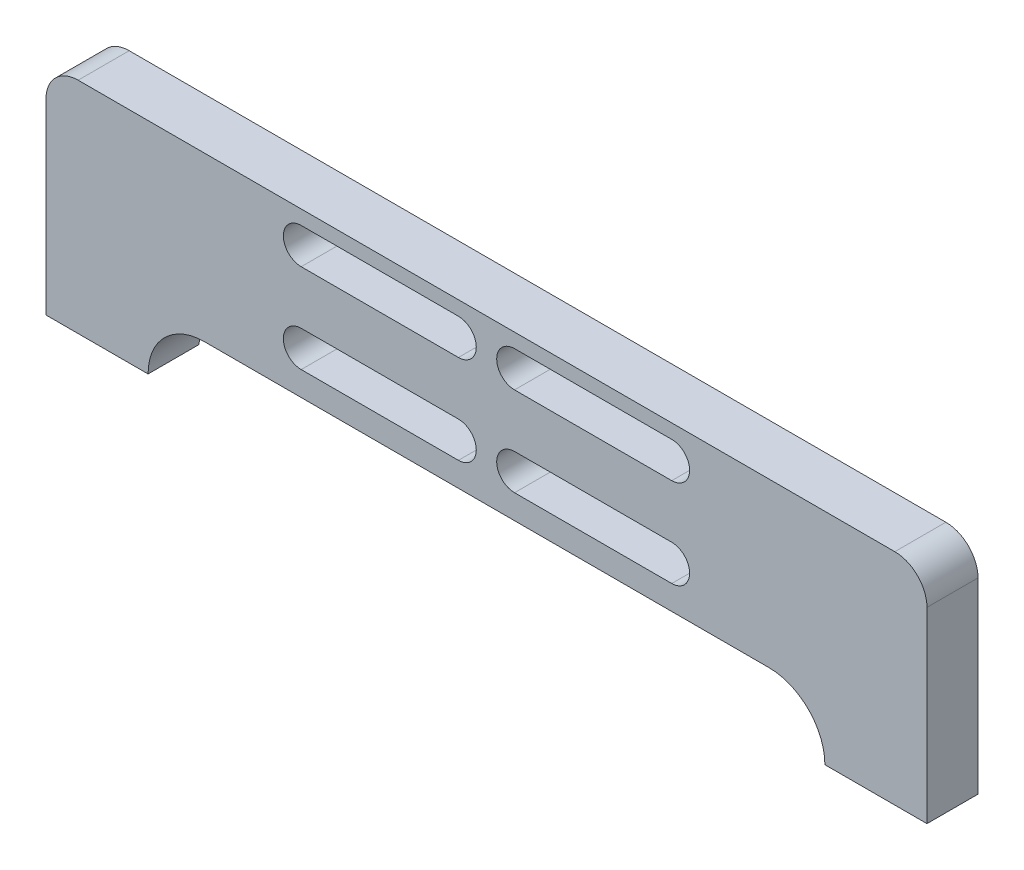
SolidWorks part; units mm, degrees
ref_plane "Front Plane" through (0, 0, 0) normal (0, 0, 1) x (1, 0, 0)
ref_plane "Top Plane" through (0, 0, 0) normal (0, 1, 0) x (1, 0, 0)
ref_plane "Right Plane" through (0, 0, 0) normal (1, 0, 0) x (0, 0, -1)
sketch "Sketch1" plane through (0, 0, 0) normal (0, 0, 1) x (1, 0, 0)
  line L0 (-79.0453, -25.7) -> (80.9547, -25.7) construction
  line L1 (-79.0453, 29.8613) -> (-79.0453, -49.0079) construction
  line L2 (80.9547, 29.8613) -> (80.9547, -49.0079) construction
  line L3 (-85.3453, -25.7) -> (87.2547, -25.7)
  line L4 (87.2547, -25.7) -> (87.2547, 0)
  line L5 (-79.0453, 6.3) -> (80.9547, 6.3)
  line L6 (-85.3453, 0) -> (-85.3453, -25.7)
  line L8 (-83.3453, -11.2) -> (-70.8453, -11.2)
  line L9 (-83.3453, -11.2) -> (-83.3453, -23.7)
  line L10 (-83.3453, -23.7) -> (-70.8453, -23.7)
  line L11 (-70.8453, -11.2) -> (-70.8453, -23.7)
  line L12 (85.2547, -11.2) -> (72.7547, -11.2)
  line L13 (85.2547, -11.2) -> (85.2547, -23.7)
  line L14 (85.2547, -23.7) -> (72.7547, -23.7)
  line L15 (72.7547, -11.2) -> (72.7547, -23.7)
  circle A0 centre (-79.0453, 0) radius 4.3
  circle A1 centre (80.9547, 0) radius 4.3
  arc A2 (-79.0453, 6.3) -> (-85.3453, 0) centre (-79.0453, 0) ccw
  arc A3 (80.9547, 6.3) -> (87.2547, 0) centre (80.9547, 0) cw
  dimension "D2" = 8.6
  dimension "D3" = 8.6
  dimension "D4" = 6.3
  dimension "D5" = 6.3
  dimension "D1" = 160
  dimension "D6" = 32
  dimension "D7" = 2
  dimension "D8" = 2
  dimension "D9" = 12.5
  dimension "D10" = 12.5
  dimension "D11" = 2
  dimension "D12" = 2
  dimension "D13" = 12.5
  dimension "D14" = 12.5
extrude "Boss-Extrude1" add sketch "Sketch1" along normal blind 8
sketch "Sketch2" plane through (0, 0, 8) normal (0, 0, 1) x (1, 0, 0)
  line L0 (-79.0453, 0) -> (80.9547, 0) construction
  line L1 (-35.3453, 6.3) -> (-35.3453, -25.7) construction
  line L2 (80.9547, 6.3) -> (-79.0453, 6.3) construction
  line L3 (-85.3453, -25.7) -> (87.2547, -25.7) construction
  line L4 (-70.8453, -17.45) -> (72.7547, -17.45) construction
  line L5 (-70.8453, -23.7) -> (-70.8453, -11.2) construction
  line L6 (72.7547, -11.2) -> (72.7547, -23.7) construction
  line L7 (37.2547, 6.3) -> (37.2547, -25.7) construction
  line L8 (-85.3453, 0) -> (-85.3453, -25.7) construction
  line L9 (87.2547, -25.7) -> (87.2547, 0) construction
  line L10 (-35.3453, 3.5) -> (37.2547, 3.5)
  line L11 (-35.3453, -3.5) -> (37.2547, -3.5)
  line L12 (-35.3453, -13.95) -> (37.2547, -13.95)
  line L13 (-35.3453, -20.95) -> (34.6432, -20.95)
  line L14 (34.6432, -20.95) -> (37.2547, -20.95)
  arc A0 (-35.3453, 3.5) -> (-35.3453, -3.5) centre (-35.3453, 0) ccw
  arc A1 (37.2547, 3.5) -> (37.2547, -3.5) centre (37.2547, 0) cw
  arc A2 (-35.3453, -13.95) -> (-35.3453, -20.95) centre (-35.3453, -17.45) ccw
  arc A3 (37.2547, -13.95) -> (37.2547, -20.95) centre (37.2547, -17.45) cw
  dimension "D1" = 50
  dimension "D2" = 50
extrude "Cut-Extrude1" cut sketch "Sketch2" against normal blind 8
extrude "Boss-Extrude2" add sketch "Sketch1<2>" along normal blind 10
sketch "Sketch1<2>" plane through (0, 0, 0) normal (0, 0, 1) x (1, 0, 0) same geometry as "Sketch1"
extrude "Cut-Extrude2" cut sketch "Sketch2<2>" against normal through all both and the other way through all
sketch "Sketch2<2>" plane through (0, 0, 8) normal (0, 0, 1) x (1, 0, 0) same geometry as "Sketch2"
sketch "Sketch3" plane through (0, 0, 10) normal (0, 0, 1) x (1, 0, 0)
  line L1 (-83.3453, -11.2) -> (-70.8453, -11.2)
  line L2 (-83.3453, -11.2) -> (-83.3453, -23.7)
  line L3 (-83.3453, -23.7) -> (-70.8453, -23.7)
  line L4 (-70.8453, -11.2) -> (-70.8453, -23.7)
  line L5 (72.7547, -11.2) -> (85.2547, -11.2)
  line L6 (72.7547, -11.2) -> (72.7547, -23.7)
  line L7 (72.7547, -23.7) -> (85.2547, -23.7)
  line L8 (85.2547, -11.2) -> (85.2547, -23.7)
extrude "Boss-Extrude3" add sketch "Sketch3" against normal blind 2
sketch "Sketch4" plane through (0, 0, 10) normal (0, 0, 1) x (1, 0, 0)
  circle A0 centre (-79.0453, 0) radius 4.3
  circle A1 centre (80.9547, 0) radius 4.3
extrude "Boss-Extrude5" add sketch "Sketch4" against normal blind 2
sketch "Sketch5" plane through (0, 0, 10) normal (0, 0, 1) x (1, 0, 0)
  line L0 (0.9547, 3.5) -> (0.9547, -20.95) construction
  line L1 (37.2547, 3.5) -> (-35.3453, 3.5) construction
  line L2 (-35.3453, -20.95) -> (37.2547, -20.95) construction
  line L3 (-38.8453, -17.45) -> (40.7547, -17.45) construction
  line L4 (-38.8453, 0) -> (40.7547, 0) construction
  line L6 (-35.3453, -3.5) -> (37.2547, -3.5) construction
  line L7 (-4.5453, 3.5) -> (6.4547, 3.5)
  line L8 (-4.5453, -3.5) -> (6.4547, -3.5)
  arc A0 (-35.3453, -13.95) -> (-35.3453, -20.95) centre (-35.3453, -17.45) ccw construction
  arc A1 (37.2547, -20.95) -> (37.2547, -13.95) centre (37.2547, -17.45) ccw construction
  arc A2 (-35.3453, 3.5) -> (-35.3453, -3.5) centre (-35.3453, 0) ccw construction
  arc A3 (37.2547, -3.5) -> (37.2547, 3.5) centre (37.2547, 0) ccw construction
  arc A4 (-4.5453, 3.5) -> (-4.5453, -3.5) centre (-4.5453, 0) cw
  arc A5 (6.4547, 3.5) -> (6.4547, -3.5) centre (6.4547, 0) ccw
  point P22 (-4.5453, 0)
  point P23 (6.4547, 0)
  dimension "D1" = 5.5
  dimension "D2" = 5.5
extrude "Boss-Extrude6" add sketch "Sketch5" against normal blind 10
sketch "Sketch6" plane through (0, 0, 10) normal (0, 0, 1) x (1, 0, 0)
  line L0 (0.9547, -13.95) -> (0.9547, -20.95) construction
  line L1 (37.2547, -13.95) -> (-35.3453, -13.95) construction
  line L2 (-35.3453, -20.95) -> (37.2547, -20.95) construction
  line L3 (-38.8453, -17.45) -> (40.7547, -17.45) construction
  line L4 (-4.5453, -13.95) -> (6.4547, -13.95)
  line L5 (-4.5453, -20.95) -> (6.4547, -20.95)
  arc A0 (-35.3453, -13.95) -> (-35.3453, -20.95) centre (-35.3453, -17.45) ccw construction
  arc A1 (37.2547, -20.95) -> (37.2547, -13.95) centre (37.2547, -17.45) ccw construction
  arc A2 (-4.5453, -13.95) -> (-4.5453, -20.95) centre (-4.5453, -17.45) cw
  arc A3 (6.4547, -13.95) -> (6.4547, -20.95) centre (6.4547, -17.45) ccw
  point P14 (6.4547, -17.45)
  point P15 (-4.5453, -17.45)
  dimension "D1" = 5.5
  dimension "D2" = 5.5
extrude "Boss-Extrude7" add sketch "Sketch6" against normal blind 10
sketch "Sketch7" plane through (0, 0, 10) normal (0, 0, 1) x (1, 0, 0)
  line L0 (-85.3453, -25.7) -> (-85.3453, -36.7)
  line L1 (-85.3453, -36.7) -> (-65.3453, -36.7)
  line L2 (87.2547, -25.7) -> (87.2547, -36.7)
  line L3 (87.2547, -36.7) -> (67.2547, -36.7)
  line L4 (-85.3453, -25.7) -> (87.2547, -25.7) construction
  line L5 (-85.3453, -25.7) -> (-54.3453, -25.7)
  line L6 (87.2547, -25.7) -> (56.2547, -25.7)
  arc A0 (-65.3453, -36.7) -> (-54.3453, -25.7) centre (-54.3453, -36.7) cw
  arc A1 (67.2547, -36.7) -> (56.2547, -25.7) centre (56.2547, -36.7) ccw
  point P7 (-54.3453, -36.7)
  point P9 (56.2547, -36.7)
  dimension "D1" = 20
  dimension "D2" = 20
  dimension "D3" = 11
  dimension "D4" = 11
  dimension "D5" = 11
  dimension "D6" = 11
extrude "Boss-Extrude8" add sketch "Sketch7" against normal blind 10
